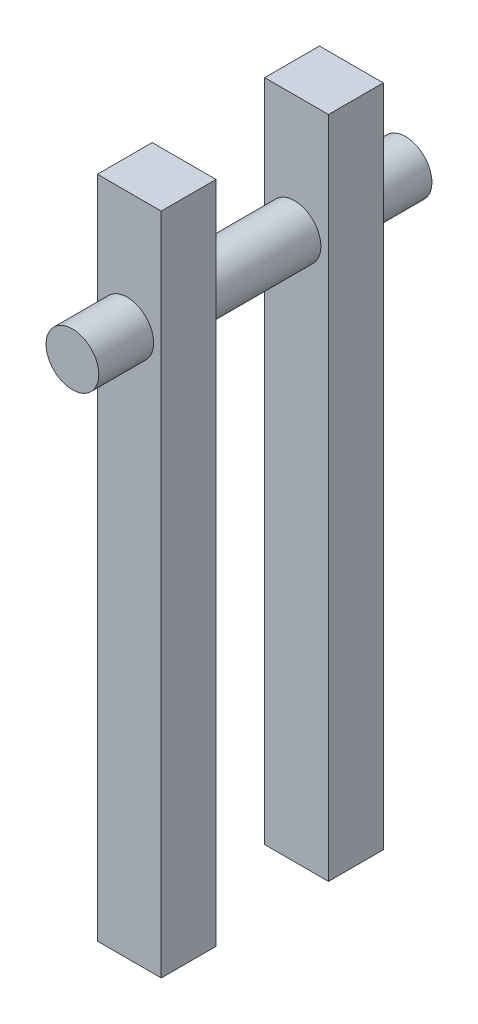
SolidWorks part; units mm, degrees
ref_plane "Front Plane" through (0, 0, 0) normal (0, 0, 1) x (1, 0, 0)
ref_plane "Top Plane" through (0, 0, 0) normal (0, 1, 0) x (1, 0, 0)
ref_plane "Right Plane" through (0, 0, 0) normal (1, 0, 0) x (0, 0, -1)
sketch "Sketch1" plane through (0, 0, 0) normal (1, 0, 0) x (0, 0, -1)
  line L0 (-32.1217, 47.1792) -> (-24.2217, 47.1792)
  line L1 (-8.0217, 47.1792) -> (-0.1217, 47.1792)
  line L2 (-8.0217, 47.1792) -> (-8.0217, -48.5208)
  line L3 (-8.0217, -48.5208) -> (-0.1217, -48.5208)
  line L4 (-0.1217, 47.1792) -> (-0.1217, -48.5208)
  line L5 (-32.1217, 47.1792) -> (-32.1217, -48.5208)
  line L6 (-32.1217, -48.5208) -> (-24.2217, -48.5208)
  line L7 (-24.2217, 47.1792) -> (-24.2217, -48.5208)
  dimension "D1" = 7.9
  dimension "D2" = 95.7
  dimension "D3" = 16.2
extrude "Boss-Extrude1" add sketch "Sketch1" along normal blind 9.2 contours L7 L6 L5 L0
extrude "Boss-Extrude2" add sketch "Sketch1<3>" along normal blind 9.2
sketch "Sketch1<3>" plane through (0, 0, 0) normal (1, 0, 0) x (0, 0, -1) same geometry as "Sketch1"
sketch "Sketch2" plane through (0, 0, 8.0217) normal (0, 0, 1) x (1, 0, 0)
  line L0 (9.2, 47.1792) -> (0, 47.1792) construction
  line L1 (9.2, 47.1792) -> (9.2, -48.5208) construction
  circle A0 centre (4.3, 30.1792) radius 3.8
  dimension "D1" = 7.6
  dimension "D2" = 17
  dimension "D3" = 4.9
extrude "Boss-Extrude3" add sketch "Sketch2" along normal blind 32 and the other way blind 16
